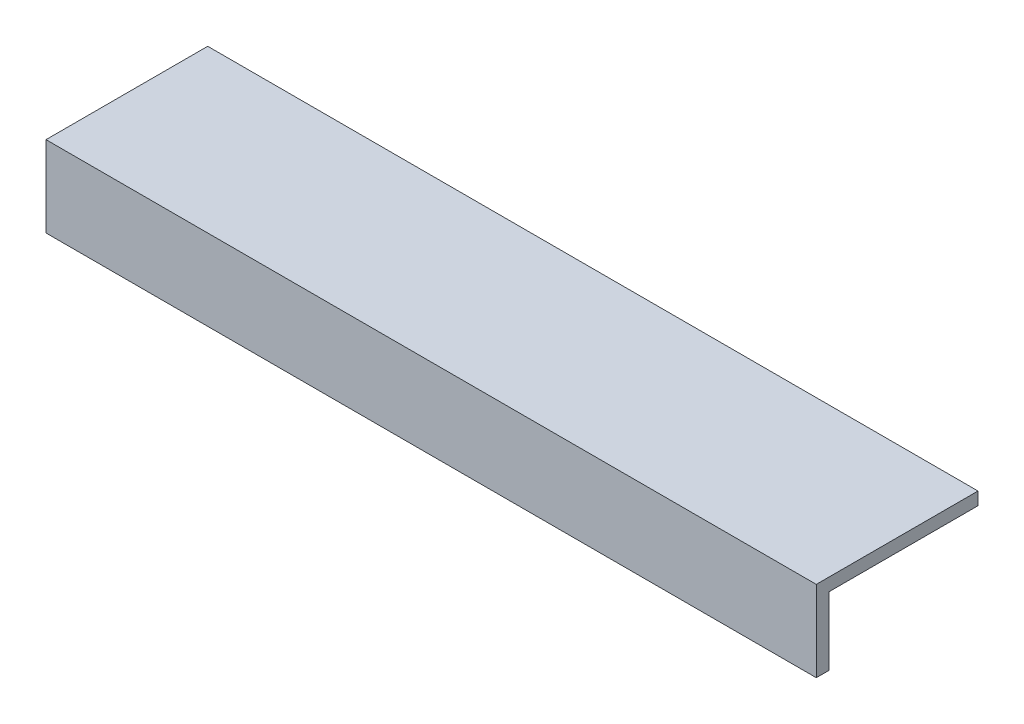
SolidWorks part; units mm, degrees
ref_plane "Alzado" through (0, 0, 0) normal (0, 0, 1) x (1, 0, 0)
ref_plane "Planta" through (0, 0, 0) normal (0, 1, 0) x (1, 0, 0)
ref_plane "Vista lateral" through (0, 0, 0) normal (1, 0, 0) x (0, 0, -1)
sketch "Croquis1" plane through (0, 0, 0) normal (1, 0, 0) x (0, 0, -1)
  line L0 (0, 0) -> (0, -38)
  line L1 (0, 0) -> (38, 0)
  line L2 (3, -3) -> (38, -3)
  line L3 (3, -3) -> (3, -38)
  line L4 (0, -38) -> (3, -38)
  line L5 (38, 0) -> (38, -3)
  dimension "D1" = 38
  dimension "D2" = 3
extrude "Saliente-Extruir1" add sketch "Croquis1" along normal blind 181
sketch "Croquis2" plane through (0, 0, 0) normal (0, 0, 1) x (1, 0, 0)
  line L0 (0, -19) -> (181, -19)
  line L1 (0, 0) -> (0, -38) construction
  line L2 (181, 0) -> (181, -38) construction
  line L3 (0, -19) -> (0, -38)
  line L4 (0, -38) -> (181, -38)
  line L5 (181, -38) -> (181, -19)
extrude "Cortar-Extruir1" cut sketch "Croquis2" against normal up to surface (3 mm away) up to face at (90.5, -20.5, -3)
